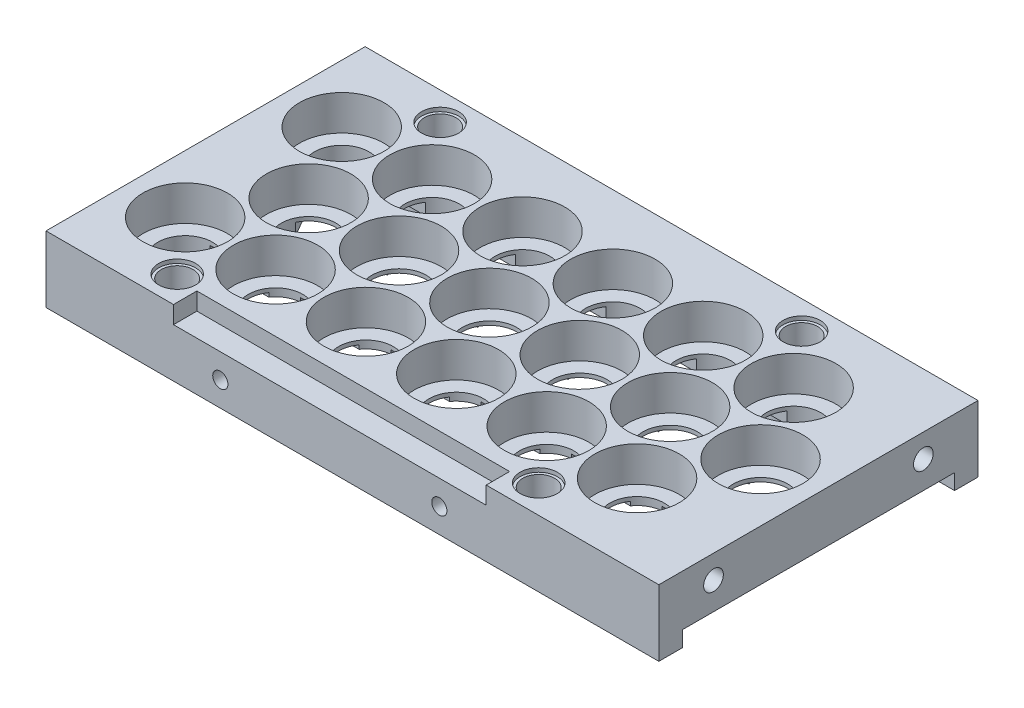
SolidWorks part; units mm, degrees
ref_plane "Front Plane" through (0, 0, 0) normal (0, 0, 1) x (1, 0, 0)
ref_plane "Top Plane" through (0, 0, 0) normal (0, 1, 0) x (1, 0, 0)
ref_plane "Right Plane" through (0, 0, 0) normal (1, 0, 0) x (0, 0, -1)
sketch "Sketch1" plane through (0, 0, 0) normal (0, 1, 0) x (1, 0, 0)
  line L0 (0, 0) -> (11.575, -20.0485) construction
  line L1 (11.575, -20.0485) -> (0, -40.097) construction
  line L2 (0, 0) -> (11.575, 0) construction
  line L3 (11.575, 0) -> (11.575, -20.0485) construction
  line L4 (11.575, -20.0485) -> (11.575, -40.097) construction
  line L5 (11.575, -40.097) -> (0, -40.097) construction
  line L6 (0, 0) -> (23.15, 0) construction
  line L7 (0, 0) -> (23.15, 0) construction
  line L8 (-14.825, -60.922) -> (142.15, -60.922)
  line L9 (-14.825, -60.922) -> (-14.825, 20.825)
  line L10 (-14.825, 20.825) -> (142.15, 20.825)
  line L11 (142.15, -60.922) -> (142.15, 20.825)
  circle A0 centre (0, 0) radius 10.825
  circle A1 centre (11.575, -20.0485) radius 10.825
  circle A2 centre (0, -40.097) radius 10.825
  circle A3 centre (23.15, 0) radius 10.825
  circle A4 centre (34.725, -20.0485) radius 10.825
  circle A5 centre (23.15, -40.097) radius 10.825
  circle A6 centre (46.3, 0) radius 10.825
  circle A7 centre (57.875, -20.0485) radius 10.825
  circle A8 centre (46.3, -40.097) radius 10.825
  circle A9 centre (69.45, 0) radius 10.825
  circle A10 centre (81.025, -20.0485) radius 10.825
  circle A11 centre (69.45, -40.097) radius 10.825
  circle A12 centre (92.6, 0) radius 10.825
  circle A13 centre (104.175, -20.0485) radius 10.825
  circle A14 centre (92.6, -40.097) radius 10.825
  circle A15 centre (115.75, 0) radius 10.825
  circle A16 centre (127.325, -20.0485) radius 10.825
  circle A17 centre (115.75, -40.097) radius 10.825
  circle A18 centre (0, 0) radius 7
  circle A19 centre (11.575, -20.0485) radius 7
  circle A20 centre (0, -40.097) radius 7
  circle A21 centre (23.15, 0) radius 7
  circle A22 centre (34.725, -20.0485) radius 7
  circle A23 centre (23.15, -40.097) radius 7
  circle A24 centre (46.3, 0) radius 7
  circle A25 centre (57.875, -20.0485) radius 7
  circle A26 centre (46.3, -40.097) radius 7
  circle A27 centre (69.45, 0) radius 7
  circle A28 centre (81.025, -20.0485) radius 7
  circle A29 centre (69.45, -40.097) radius 7
  circle A30 centre (92.6, 0) radius 7
  circle A31 centre (104.175, -20.0485) radius 7
  circle A32 centre (92.6, -40.097) radius 7
  circle A33 centre (115.75, 0) radius 7
  circle A34 centre (127.325, -20.0485) radius 7
  circle A35 centre (115.75, -40.097) radius 7
  dimension "D3" = 21.65
  dimension "D11" = 14
  dimension "D1" = 60
  dimension "D2" = 60
  dimension "D4" = 1.5
  dimension "D6" = 23.15
  dimension "D7" = 4
  dimension "D8" = 4
  dimension "D9" = 10
  dimension "D10" = 10
  dimension "D13" = 23.15
  dimension "D5" = 6
  dimension "D12" = 6
extrude "Boss-Extrude2" add sketch "Sketch1" along normal blind 11 contours L8 L11 L10 L9 A17 A16 A15 A14 A13 A12 A11 A10 A9 A8 A7 A6 A5 A4 A3 A2 A1 A0 region at (-13.0551, 0, 20.0485)
extrude "Boss-Extrude3" add sketch "Sketch1<3>" along normal blind 2 contours A0 A18 | A3 A21 | A6 A24 | A9 A27 | A12 A30 | A15 A33 | A1 A19 | A4 A22 | A7 A25 | A10 A28 | A13 A31 | A16 A34 | A17 A35 | A14 A32 | A11 A29 | A8 A26 | A5 A23 | A2 A20 region at (-10.5188, 0, 0) region at (1.0562, 0, 20.0485) region at (-10.5188, 0, 40.097) region at (12.6312, 0, 0) region at (24.2062, 0, 20.0485) region at (12.6312, 0, 40.097) region at (35.7812, 0, 0) region at (47.3562, 0, 20.0485) region at (35.7812, 0, 40.097) region at (58.9312, 0, 0) region at (70.5062, 0, 20.0485) region at (58.9312, 0, 40.097) region at (82.0812, 0, 0) region at (93.6562, 0, 20.0485) region at (82.0812, 0, 40.097) region at (105.2312, 0, 0) region at (116.8062, 0, 20.0485) region at (105.2312, 0, 40.097)
sketch "Sketch1<3>" plane through (0, 0, 0) normal (0, 1, 0) x (1, 0, 0) same geometry as "Sketch1"
sketch "Sketch2" plane through (0, 0, 0) normal (0, -1, 0) x (1, 0, 0)
  line L0 (0, 40.097) -> (11.575, 20.0485) construction
  line L1 (3.4641, 42.097) -> (15.0391, 22.0485)
  line L2 (-3.4641, 38.097) -> (8.1109, 18.0485)
  line L3 (11.575, 20.0485) -> (0, 0) construction
  line L4 (15.0391, 18.0485) -> (3.4641, -2)
  line L5 (8.1109, 22.0485) -> (-3.4641, 2)
  line L6 (19.6859, 38.097) -> (31.2609, 18.0485)
  line L7 (26.6141, 42.097) -> (38.1891, 22.0485)
  line L8 (31.2609, 22.0485) -> (19.6859, 2)
  line L9 (38.1891, 18.0485) -> (26.6141, -2)
  line L10 (23.15, 40.097) -> (34.725, 20.0485) construction
  line L11 (34.725, 20.0485) -> (23.15, 0) construction
  line L12 (42.8359, 38.097) -> (54.4109, 18.0485)
  line L13 (49.7641, 42.097) -> (61.3391, 22.0485)
  line L14 (54.4109, 22.0485) -> (42.8359, 2)
  line L15 (61.3391, 18.0485) -> (49.7641, -2)
  line L16 (46.3, 40.097) -> (57.875, 20.0485) construction
  line L17 (57.875, 20.0485) -> (46.3, 0) construction
  line L18 (65.9859, 38.097) -> (77.5609, 18.0485)
  line L19 (72.9141, 42.097) -> (84.4891, 22.0485)
  line L20 (77.5609, 22.0485) -> (65.9859, 2)
  line L21 (84.4891, 18.0485) -> (72.9141, -2)
  line L22 (69.45, 40.097) -> (81.025, 20.0485) construction
  line L23 (81.025, 20.0485) -> (69.45, 0) construction
  line L24 (89.1359, 38.097) -> (100.7109, 18.0485)
  line L25 (96.0641, 42.097) -> (107.6391, 22.0485)
  line L26 (100.7109, 22.0485) -> (89.1359, 2)
  line L27 (107.6391, 18.0485) -> (96.0641, -2)
  line L28 (92.6, 40.097) -> (104.175, 20.0485) construction
  line L29 (104.175, 20.0485) -> (92.6, 0) construction
  line L30 (112.2859, 38.097) -> (123.8609, 18.0485)
  line L31 (119.2141, 42.097) -> (130.7891, 22.0485)
  line L32 (123.8609, 22.0485) -> (112.2859, 2)
  line L33 (130.7891, 18.0485) -> (119.2141, -2)
  line L34 (115.75, 40.097) -> (127.325, 20.0485) construction
  line L35 (127.325, 20.0485) -> (115.75, 0) construction
  line L36 (-3.4641, 38.097) -> (19.6859, 38.097) construction
  line L37 (0, 40.097) -> (115.75, 40.097) construction
  line L38 (0, 44.097) -> (115.75, 44.097)
  line L39 (0, 36.097) -> (115.75, 36.097)
  line L40 (11.575, 20.0485) -> (127.325, 20.0485) construction
  line L41 (11.575, 24.0485) -> (127.325, 24.0485)
  line L42 (11.575, 16.0485) -> (127.325, 16.0485)
  line L43 (0, 0) -> (115.75, 0) construction
  line L44 (0, 4) -> (115.75, 4)
  line L45 (0, -4) -> (115.75, -4)
  arc A0 (3.4641, 42.097) -> (-3.4641, 38.097) centre (0, 40.097) ccw
  arc A1 (8.1109, 18.0485) -> (15.0391, 22.0485) centre (11.575, 20.0485) ccw
  arc A2 (15.0391, 18.0485) -> (8.1109, 22.0485) centre (11.575, 20.0485) ccw
  arc A3 (-3.4641, 2) -> (3.4641, -2) centre (0, 0) ccw
  arc A4 (26.6141, 42.097) -> (19.6859, 38.097) centre (23.15, 40.097) ccw
  arc A5 (31.2609, 18.0485) -> (38.1891, 22.0485) centre (34.725, 20.0485) ccw
  arc A6 (38.1891, 18.0485) -> (31.2609, 22.0485) centre (34.725, 20.0485) ccw
  arc A7 (19.6859, 2) -> (26.6141, -2) centre (23.15, 0) ccw
  arc A8 (49.7641, 42.097) -> (42.8359, 38.097) centre (46.3, 40.097) ccw
  arc A9 (54.4109, 18.0485) -> (61.3391, 22.0485) centre (57.875, 20.0485) ccw
  arc A10 (61.3391, 18.0485) -> (54.4109, 22.0485) centre (57.875, 20.0485) ccw
  arc A11 (42.8359, 2) -> (49.7641, -2) centre (46.3, 0) ccw
  arc A12 (72.9141, 42.097) -> (65.9859, 38.097) centre (69.45, 40.097) ccw
  arc A13 (77.5609, 18.0485) -> (84.4891, 22.0485) centre (81.025, 20.0485) ccw
  arc A14 (84.4891, 18.0485) -> (77.5609, 22.0485) centre (81.025, 20.0485) ccw
  arc A15 (65.9859, 2) -> (72.9141, -2) centre (69.45, 0) ccw
  arc A16 (96.0641, 42.097) -> (89.1359, 38.097) centre (92.6, 40.097) ccw
  arc A17 (100.7109, 18.0485) -> (107.6391, 22.0485) centre (104.175, 20.0485) ccw
  arc A18 (107.6391, 18.0485) -> (100.7109, 22.0485) centre (104.175, 20.0485) ccw
  arc A19 (89.1359, 2) -> (96.0641, -2) centre (92.6, 0) ccw
  arc A20 (119.2141, 42.097) -> (112.2859, 38.097) centre (115.75, 40.097) ccw
  arc A21 (123.8609, 18.0485) -> (130.7891, 22.0485) centre (127.325, 20.0485) ccw
  arc A22 (130.7891, 18.0485) -> (123.8609, 22.0485) centre (127.325, 20.0485) ccw
  arc A23 (112.2859, 2) -> (119.2141, -2) centre (115.75, 0) ccw
  arc A24 (0, 44.097) -> (0, 36.097) centre (0, 40.097) ccw
  arc A25 (115.75, 36.097) -> (115.75, 44.097) centre (115.75, 40.097) ccw
  arc A26 (11.575, 24.0485) -> (11.575, 16.0485) centre (11.575, 20.0485) ccw
  arc A27 (127.325, 16.0485) -> (127.325, 24.0485) centre (127.325, 20.0485) ccw
  arc A28 (0, 4) -> (0, -4) centre (0, 0) ccw
  arc A29 (115.75, -4) -> (115.75, 4) centre (115.75, 0) ccw
  point P3 (5.7875, 30.0727)
  point P8 (5.7875, 10.0242)
  point P18 (28.9375, 30.0727)
  point P25 (28.9375, 10.0242)
  point P34 (52.0875, 30.0727)
  point P39 (52.0875, 10.0242)
  point P48 (75.2375, 30.0727)
  point P53 (75.2375, 10.0242)
  point P62 (98.3875, 30.0727)
  point P67 (98.3875, 10.0242)
  point P76 (121.5375, 30.0727)
  point P81 (121.5375, 10.0242)
  point P91 (57.875, 40.097)
  point P96 (69.45, 20.0485)
  point P103 (57.875, 0)
  circle M62 centre (0, 0) radius 7
  circle M63 centre (23.15, 0) radius 7
  circle M64 centre (46.3, 0) radius 7
  circle M65 centre (69.45, 0) radius 7
  circle M66 centre (92.6, 0) radius 7
  circle M67 centre (115.75, 0) radius 7
  circle M68 centre (11.575, 20.0485) radius 7
  circle M69 centre (34.725, 20.0485) radius 7
  circle M70 centre (57.875, 20.0485) radius 7
  circle M71 centre (81.025, 20.0485) radius 7
  circle M72 centre (104.175, 20.0485) radius 7
  circle M73 centre (127.325, 20.0485) radius 7
  circle M74 centre (115.75, 40.097) radius 7
  circle M75 centre (92.6, 40.097) radius 7
  circle M76 centre (69.45, 40.097) radius 7
  circle M77 centre (46.3, 40.097) radius 7
  circle M78 centre (23.15, 40.097) radius 7
  circle M79 centre (0, 40.097) radius 7
  dimension "D1" = 8
  dimension "D3" = 23.15
  dimension "D4" = 8
  dimension "D5" = 8
  dimension "D6" = 8
extrude "Cut-Extrude1" cut sketch "Sketch2" against normal blind 1 contours L1 L39 L38 M78 M79 | L7 L39 L38 M77 M78 | L39 L2 L1 M79 M68 | L42 L8 L6 L41 M68 M69 | L6 L41 L7 L39 M69 M78 | L12 L41 L13 L39 M70 M77 | L13 L39 L38 M76 M77 | L18 L41 L19 L39 M71 M76 | L19 L39 L38 M75 M76 | L24 L41 L25 L39 M72 M75 | L25 L39 L38 M74 M75 | L30 L41 L31 M73 M74 | L42 L32 L30 L41 M72 M73 | L42 L26 L24 L41 M71 M72 | L42 L20 L18 L41 M70 M71 | L42 L14 L12 L41 M69 M70 | L45 L44 L4 M62 M63 | L44 L4 L5 M62 M68 | L45 L44 L9 M63 M64 | L45 L44 L15 M64 M65 | L45 L44 L21 M65 M66 | L45 L44 L27 M66 M67 | L44 L27 L42 L26 M66 M72 | L42 L32 L33 M67 M73 | L44 L21 L42 L20 M65 M71 | L44 L15 L42 L14 M64 M70 | L39 L13 M77 | L39 L25 M75 | L39 L19 M76 | L41 L6 M69 | L44 L4 M62 | L44 L15 M64 | L44 L21 M65 | L44 L27 M66 | L41 L30 M73 | L32 L42 M73 | L41 L24 M72 | L26 L42 M72 | L41 L18 M71 | L20 L42 M71 | L41 L12 M70 | L14 L42 M70 | L44 L9 L42 L8 M63 M69 | L8 L42 M69 | L39 L7 M78 | L39 L1 M79 | L44 A29 L45 A28 region at (11.6138, 0, 40.1242) region at (6.3461, 0, 36.4331) region at (5.7834, 0, 30.0255) region at (23.0718, 0, 20.0485) region at (28.9375, 0, 30.0727) region at (34.7638, 0, 40.1242) region at (28.3789, 0, 23.7124) region at (5.7834, 0, 10.0715) region at (29.4961, 0, 36.4331) region at (57.9138, 0, 40.1242) region at (28.3789, 0, 16.3846) region at (28.9375, 0, 10.0242) region at (6.3461, 0, 3.6639) region at (11.6138, 0, -0.0272) region at (52.0875, 0, 30.0727) region at (46.2218, 0, 20.0485) region at (52.6461, 0, 36.4331) region at (81.0638, 0, 40.1242) region at (51.5289, 0, 23.7124) region at (34.7638, 0, -0.0272) region at (75.2375, 0, 30.0727) region at (75.7961, 0, 36.4331) region at (104.2138, 0, 40.1242) region at (74.6789, 0, 23.7124) region at (69.3718, 0, 20.0485) region at (51.5289, 0, 16.3846) region at (52.0875, 0, 10.0242) region at (57.9138, 0, -0.0272) region at (98.3875, 0, 30.0727) region at (98.9461, 0, 36.4331) region at (97.8289, 0, 23.7124) region at (92.5218, 0, 20.0485) region at (74.6789, 0, 16.3846) region at (52.6461, 0, 3.6639) region at (81.0638, 0, -0.0272) region at (121.5416, 0, 30.12) region at (75.2375, 0, 10.0242) region at (120.9789, 0, 23.7124) region at (115.6718, 0, 20.0485) region at (97.8289, 0, 16.3846) region at (75.7961, 0, 3.6639) region at (104.2138, 0, -0.0272) region at (98.3875, 0, 10.0242) region at (121.5416, 0, 9.977) region at (120.9789, 0, 16.3846) region at (98.9461, 0, 3.6639)
sketch "Sketch9" plane through (0, 11, 0) normal (0, 1, 0) x (1, 0, 0)
  line L0 (11.575, -60.922) -> (11.575, 20.825)
  line L1 (-14.825, 20.825) -> (142.15, 20.825) construction
  line L2 (104.175, 20.825) -> (104.175, -60.922)
  line L3 (-14.825, -60.922) -> (142.15, -60.922) construction
  circle A0 centre (11.575, 13.625) radius 4.0767
  circle A1 centre (11.575, -53.722) radius 4.0767
  circle A2 centre (104.175, -53.722) radius 4.0767
  circle A3 centre (104.175, 13.625) radius 4.0767
  point P0 (11.575, 13.625)
  point P7 (11.575, -20.0485)
  point P15 (104.175, -20.0485)
  point P20 (104.175, 13.625)
  point P21 (104.175, -53.722)
  point P22 (11.575, -53.722)
  dimension "D5" = 8.1534
  dimension "D1" = 7.2
  dimension "D4" = 7.2
extrude "Cut-Extrude3" cut sketch "Sketch9" against normal up to next contours A2 | A1 | A0 | A3
sketch "Sketch10" plane through (0, 11, 0) normal (0, 1, 0) x (1, 0, 0)
  circle A0 centre (11.575, 13.625) radius 4.7625
  circle A1 centre (104.175, 13.625) radius 4.7625
  circle A2 centre (104.175, -53.722) radius 4.7625
  circle A3 centre (11.575, -53.722) radius 4.7625
  dimension "D1" = 9.525
extrude "Cut-Extrude4" cut sketch "Sketch10" against normal blind 1
sketch "Sketch13" plane through (0, 0, 0) normal (0, -1, 0) x (1, 0, 0)
  line L0 (142.15, 60.922) -> (142.15, -20.825) construction
  line L5 (3.575, 53.722) -> (3.575, 60.922)
  line L8 (-14.825, 60.922) -> (142.15, 60.922) construction
  line L9 (3.575, 60.922) -> (19.575, 60.922)
  line L10 (19.575, 60.922) -> (19.575, 53.722)
  line L12 (57.875, 20.0485) -> (57.875, -20.825) construction
  line L13 (-14.825, -20.825) -> (142.15, -20.825) construction
  line L14 (11.575, 20.0485) -> (127.325, 20.0485) construction
  line L16 (96.175, 60.922) -> (96.175, 53.722)
  line L17 (112.175, 60.922) -> (96.175, 60.922)
  line L18 (112.175, 53.722) -> (112.175, 60.922)
  line L19 (-14.825, 60.922) -> (142.15, 60.922)
  line L20 (-14.825, 60.922) -> (-14.825, 54.922)
  line L21 (-14.825, 54.922) -> (142.15, 54.922)
  line L22 (142.15, 60.922) -> (142.15, 54.922)
  line L23 (142.15, -20.825) -> (142.15, -14.825)
  line L24 (-14.825, -14.825) -> (142.15, -14.825)
  line L25 (-14.825, -20.825) -> (-14.825, -14.825)
  line L26 (-14.825, -20.825) -> (142.15, -20.825)
  line L27 (112.175, -13.625) -> (112.175, -20.825)
  line L28 (112.175, -20.825) -> (96.175, -20.825)
  line L29 (96.175, -20.825) -> (96.175, -13.625)
  line L32 (19.575, -20.825) -> (19.575, -13.625)
  line L33 (3.575, -20.825) -> (19.575, -20.825)
  line L34 (3.575, -13.625) -> (3.575, -20.825)
  circle A4 centre (11.575, 53.722) radius 6.5
  circle A5 centre (11.575, 53.722) radius 8
  circle A6 centre (104.175, 53.722) radius 8
  circle A7 centre (104.175, 53.722) radius 6.5
  circle A8 centre (104.175, -13.625) radius 6.5
  circle A9 centre (104.175, -13.625) radius 8
  circle A10 centre (11.575, -13.625) radius 8
  circle A11 centre (11.575, -13.625) radius 6.5
  line M15 (142.15, 60.922) -> (-14.825, 60.922)
  line M16 (-14.825, 60.922) -> (-14.825, -20.825)
  line M17 (-14.825, -20.825) -> (142.15, -20.825)
  line M18 (142.15, -20.825) -> (142.15, 60.922)
  dimension "D1" = 13
  dimension "D2" = 16
  dimension "D3" = 6
extrude "Boss-Extrude7" add sketch "Sketch13" along normal blind 6 contours L21 L5 M16 M15 | A5 L5 L21 M15 | A5 L21 L10 M15 | L10 L21 L16 M15 | L21 A5 L19 A4 | A5 L21 A4 | L21 A6 L16 M15 | L21 A7 A6 L19 | L21 A7 A6 | A6 L21 L18 M15 | L18 L21 M18 M15 | A9 L24 L29 L26 | L28 A9 L24 A8 | A9 L26 L27 L24 | L24 L27 L26 M18 | L32 L26 L29 L24 | L24 A9 A8 | L34 L24 M16 M17 | L26 A10 L24 L34 | L24 A11 A10 | L24 A11 A10 L33 | L24 A10 L26 L32 region at (3.7817, 0, 54.3098) region at (-5.625, 0, 57.922) region at (4.8282, 0, 59.2567) region at (5.2714, 0, 58.3681) region at (18.3218, 0, 59.2567) region at (57.875, 0, 57.922) region at (-5.625, 0, -17.825) region at (97.4282, 0, 59.2567) region at (4.8282, 0, -19.1597) region at (96.3817, 0, 54.3098) region at (97.8714, 0, 58.3681) region at (3.7817, 0, -14.2128) region at (4.4261, 0, -14.9942) region at (110.9218, 0, 59.2567) region at (127.1625, 0, 57.922) region at (18.3218, 0, -19.1597) region at (57.875, 0, -17.825) region at (97.4282, 0, -19.1597) region at (127.1625, 0, -17.825) region at (96.3817, 0, -14.2128) region at (97.0261, 0, -14.9942) region at (110.9218, 0, -19.1597)
sketch "Sketch14" plane through (0, 0, 0) normal (0, -1, 0) x (1, 0, 0)
  line L2 (142.15, 54.922) -> (142.15, -14.825) construction
  line L4 (5.2386, 17.0736) -> (-0.5918, 6.9749) construction
  line L5 (5.7446, -4) -> (17.4054, -4) construction
  line L6 (28.8946, -4) -> (40.5554, -4) construction
  line L7 (52.0446, -4) -> (63.7054, -4) construction
  line L8 (75.1946, -4) -> (86.8554, -4) construction
  line L9 (98.3446, -4) -> (110.0054, -4) construction
  line L10 (127.9168, 13.0736) -> (122.0864, 2.9749) construction
  line L11 (122.0864, 37.122) -> (127.9168, 27.0234) construction
  line L12 (98.3446, 44.097) -> (110.0054, 44.097) construction
  line L13 (75.1946, 44.097) -> (86.8554, 44.097) construction
  line L14 (52.0446, 44.097) -> (63.7054, 44.097) construction
  line L15 (28.8946, 44.097) -> (40.5554, 44.097) construction
  line L16 (-0.5918, 33.122) -> (5.2386, 23.0234) construction
  line L17 (5.7446, 44.097) -> (17.4054, 44.097) construction
  line L20 (142.15, 54.922) -> (142.15, -14.825)
  line L22 (5.2386, 17.0736) -> (-0.5918, 6.9749)
  line L23 (5.7446, -4) -> (17.4054, -4)
  line L24 (28.8946, -4) -> (40.5554, -4)
  line L25 (52.0446, -4) -> (63.7054, -4)
  line L26 (75.1946, -4) -> (86.8554, -4)
  line L27 (98.3446, -4) -> (110.0054, -4)
  line L28 (127.9168, 13.0736) -> (122.0864, 2.9749)
  line L29 (122.0864, 37.122) -> (127.9168, 27.0234)
  line L30 (98.3446, 44.097) -> (110.0054, 44.097)
  line L31 (75.1946, 44.097) -> (86.8554, 44.097)
  line L32 (52.0446, 44.097) -> (63.7054, 44.097)
  line L33 (28.8946, 44.097) -> (40.5554, 44.097)
  line L34 (-0.5918, 33.122) -> (5.2386, 23.0234)
  line L35 (5.7446, 44.097) -> (17.4054, 44.097)
  line L36 (112.0845, -14.825) -> (142.15, -14.825) construction
  line L37 (19.4845, -14.825) -> (96.2655, -14.825) construction
  line L38 (-14.825, -14.825) -> (3.6655, -14.825) construction
  line L39 (-14.825, 54.922) -> (-14.825, -14.825) construction
  line L40 (112.0845, 54.922) -> (142.15, 54.922) construction
  line L41 (19.4845, 54.922) -> (96.2655, 54.922) construction
  line L42 (-14.825, 54.922) -> (3.6655, 54.922) construction
  line L43 (112.0845, -14.825) -> (142.15, -14.825)
  line L44 (19.4845, -14.825) -> (96.2655, -14.825)
  line L45 (-14.825, -14.825) -> (3.6655, -14.825)
  line L46 (-14.825, 54.922) -> (-14.825, -14.825)
  line L47 (112.0845, 54.922) -> (142.15, 54.922)
  line L48 (19.4845, 54.922) -> (96.2655, 54.922)
  line L49 (-14.825, 54.922) -> (3.6655, 54.922)
  arc A3 (5.2386, 23.0234) -> (5.2386, 17.0736) centre (11.575, 20.0485) ccw construction
  arc A4 (-0.5918, 6.9749) -> (5.7446, -4) centre (0, 0) ccw construction
  arc A5 (17.4054, -4) -> (28.8946, -4) centre (23.15, 0) ccw construction
  arc A6 (40.5554, -4) -> (52.0446, -4) centre (46.3, 0) ccw construction
  arc A7 (63.7054, -4) -> (75.1946, -4) centre (69.45, 0) ccw construction
  arc A8 (86.8554, -4) -> (98.3446, -4) centre (92.6, 0) ccw construction
  arc A9 (110.0054, -4) -> (122.0864, 2.9749) centre (115.75, 0) ccw construction
  arc A10 (127.9168, 13.0736) -> (127.9168, 27.0234) centre (127.325, 20.0485) ccw construction
  arc A11 (122.0864, 37.122) -> (110.0054, 44.097) centre (115.75, 40.097) ccw construction
  arc A12 (98.3446, 44.097) -> (86.8554, 44.097) centre (92.6, 40.097) ccw construction
  arc A13 (75.1946, 44.097) -> (63.7054, 44.097) centre (69.45, 40.097) ccw construction
  arc A14 (52.0446, 44.097) -> (40.5554, 44.097) centre (46.3, 40.097) ccw construction
  arc A16 (28.8946, 44.097) -> (17.4054, 44.097) centre (23.15, 40.097) ccw construction
  arc A17 (5.7446, 44.097) -> (-0.5918, 33.122) centre (0, 40.097) ccw construction
  arc A21 (5.2386, 23.0234) -> (5.2386, 17.0736) centre (11.575, 20.0485) ccw
  arc A22 (-0.5918, 6.9749) -> (5.7446, -4) centre (0, 0) ccw
  arc A23 (17.4054, -4) -> (28.8946, -4) centre (23.15, 0) ccw
  arc A24 (40.5554, -4) -> (52.0446, -4) centre (46.3, 0) ccw
  arc A25 (63.7054, -4) -> (75.1946, -4) centre (69.45, 0) ccw
  arc A26 (86.8554, -4) -> (98.3446, -4) centre (92.6, 0) ccw
  arc A27 (110.0054, -4) -> (122.0864, 2.9749) centre (115.75, 0) ccw
  arc A28 (127.9168, 13.0736) -> (127.9168, 27.0234) centre (127.325, 20.0485) ccw
  arc A29 (122.0864, 37.122) -> (110.0054, 44.097) centre (115.75, 40.097) ccw
  arc A30 (98.3446, 44.097) -> (86.8554, 44.097) centre (92.6, 40.097) ccw
  arc A31 (75.1946, 44.097) -> (63.7054, 44.097) centre (69.45, 40.097) ccw
  arc A32 (52.0446, 44.097) -> (40.5554, 44.097) centre (46.3, 40.097) ccw
  arc A34 (28.8946, 44.097) -> (17.4054, 44.097) centre (23.15, 40.097) ccw
  arc A35 (5.7446, 44.097) -> (-0.5918, 33.122) centre (0, 40.097) ccw
  arc A36 (112.0845, -14.825) -> (96.2655, -14.825) centre (104.175, -13.625) ccw construction
  arc A37 (19.4845, -14.825) -> (3.6655, -14.825) centre (11.575, -13.625) ccw construction
  arc A38 (96.2655, 54.922) -> (112.0845, 54.922) centre (104.175, 53.722) ccw construction
  arc A39 (3.6655, 54.922) -> (19.4845, 54.922) centre (11.575, 53.722) ccw construction
  arc A40 (112.0845, -14.825) -> (96.2655, -14.825) centre (104.175, -13.625) ccw
  arc A41 (19.4845, -14.825) -> (3.6655, -14.825) centre (11.575, -13.625) ccw
  arc A42 (96.2655, 54.922) -> (112.0845, 54.922) centre (104.175, 53.722) ccw
  arc A43 (3.6655, 54.922) -> (19.4845, 54.922) centre (11.575, 53.722) ccw
extrude "Boss-Extrude9" add sketch "Sketch14" along normal blind 2
sketch "Sketch16" plane through (0, 0, 0) normal (0, -1, 0) x (1, 0, 0)
  line L0 (17.4054, 36.097) -> (12.1668, 27.0234) construction
  line L1 (12.1668, 27.0234) -> (17.3196, 24.0485) construction
  line L2 (17.3196, 24.0485) -> (22.5582, 33.122) construction
  line L3 (22.5582, 33.122) -> (17.4054, 36.097) construction
  line L4 (14.7861, 31.5602) -> (19.9389, 28.5853) construction
  line L5 (15.5361, 32.8592) -> (20.6889, 29.8843)
  line L6 (14.0361, 30.2612) -> (19.1889, 27.2862)
  line L7 (11.575, 20.0485) -> (126.446, 20.0485) construction
  line L8 (40.5554, 36.097) -> (35.3168, 27.0234) construction
  line L9 (35.3168, 27.0234) -> (40.4696, 24.0485) construction
  line L10 (40.4696, 24.0485) -> (45.7082, 33.122) construction
  line L11 (45.7082, 33.122) -> (40.5554, 36.097) construction
  line L12 (37.9361, 31.5602) -> (43.0889, 28.5853) construction
  line L13 (38.6861, 32.8592) -> (43.8389, 29.8843)
  line L14 (37.1861, 30.2612) -> (42.3389, 27.2862)
  line L15 (63.7054, 36.097) -> (58.4668, 27.0234) construction
  line L16 (58.4668, 27.0234) -> (63.6196, 24.0485) construction
  line L17 (63.6196, 24.0485) -> (68.8582, 33.122) construction
  line L18 (68.8582, 33.122) -> (63.7054, 36.097) construction
  line L19 (61.0861, 31.5602) -> (66.2389, 28.5853) construction
  line L20 (61.8361, 32.8592) -> (66.9889, 29.8843)
  line L21 (60.3361, 30.2612) -> (65.4889, 27.2862)
  line L22 (86.8554, 36.097) -> (81.6168, 27.0234) construction
  line L23 (81.6168, 27.0234) -> (86.7696, 24.0485) construction
  line L24 (86.7696, 24.0485) -> (92.0082, 33.122) construction
  line L25 (92.0082, 33.122) -> (86.8554, 36.097) construction
  line L26 (84.2361, 31.5602) -> (89.3889, 28.5853) construction
  line L27 (84.9861, 32.8592) -> (90.1389, 29.8843)
  line L28 (83.4861, 30.2612) -> (88.6389, 27.2862)
  line L29 (110.0054, 36.097) -> (104.7668, 27.0234) construction
  line L30 (104.7668, 27.0234) -> (109.9196, 24.0485) construction
  line L31 (109.9196, 24.0485) -> (115.1582, 33.122) construction
  line L32 (115.1582, 33.122) -> (110.0054, 36.097) construction
  line L33 (107.3861, 31.5602) -> (112.5389, 28.5853) construction
  line L34 (108.1361, 32.8592) -> (113.2889, 29.8843)
  line L35 (106.6361, 30.2612) -> (111.7889, 27.2862)
  line L36 (14.7861, 8.5368) -> (19.9389, 11.5117) construction
  line L37 (15.5361, 7.2377) -> (20.6889, 10.2127)
  line L38 (14.0361, 9.8358) -> (19.1889, 12.8108)
  line L39 (37.9361, 8.5368) -> (43.0889, 11.5117) construction
  line L40 (38.6861, 7.2377) -> (43.8389, 10.2127)
  line L41 (37.1861, 9.8358) -> (42.3389, 12.8108)
  line L42 (61.0861, 8.5368) -> (66.2389, 11.5117) construction
  line L43 (61.8361, 7.2377) -> (66.9889, 10.2127)
  line L44 (60.3361, 9.8358) -> (65.4889, 12.8108)
  line L45 (84.2361, 8.5368) -> (89.3889, 11.5117) construction
  line L46 (84.9861, 7.2377) -> (90.1389, 10.2127)
  line L47 (83.4861, 9.8358) -> (88.6389, 12.8108)
  line L48 (107.3861, 8.5368) -> (112.5389, 11.5117) construction
  line L49 (108.1361, 7.2377) -> (113.2889, 10.2127)
  line L50 (106.6361, 9.8358) -> (111.7889, 12.8108)
  line L51 (115.1582, 6.9749) -> (110.0054, 4) construction
  line L52 (109.9196, 16.0485) -> (115.1582, 6.9749) construction
  line L53 (104.7668, 13.0736) -> (109.9196, 16.0485) construction
  line L54 (110.0054, 4) -> (104.7668, 13.0736) construction
  line L55 (92.0082, 6.9749) -> (86.8554, 4) construction
  line L56 (86.7696, 16.0485) -> (92.0082, 6.9749) construction
  line L57 (81.6168, 13.0736) -> (86.7696, 16.0485) construction
  line L58 (86.8554, 4) -> (81.6168, 13.0736) construction
  line L59 (68.8582, 6.9749) -> (63.7054, 4) construction
  line L60 (63.6196, 16.0485) -> (68.8582, 6.9749) construction
  line L61 (58.4668, 13.0736) -> (63.6196, 16.0485) construction
  line L62 (63.7054, 4) -> (58.4668, 13.0736) construction
  line L63 (45.7082, 6.9749) -> (40.5554, 4) construction
  line L64 (40.4696, 16.0485) -> (45.7082, 6.9749) construction
  line L65 (35.3168, 13.0736) -> (40.4696, 16.0485) construction
  line L66 (40.5554, 4) -> (35.3168, 13.0736) construction
  line L67 (22.5582, 6.9749) -> (17.4054, 4) construction
  line L68 (17.3196, 16.0485) -> (22.5582, 6.9749) construction
  line L69 (12.1668, 13.0736) -> (17.3196, 16.0485) construction
  line L70 (17.4054, 4) -> (12.1668, 13.0736) construction
  arc A0 (15.5361, 32.8592) -> (14.0361, 30.2612) centre (14.7861, 31.5602) ccw
  arc A1 (19.1889, 27.2862) -> (20.6889, 29.8843) centre (19.9389, 28.5853) ccw
  arc A2 (38.6861, 32.8592) -> (37.1861, 30.2612) centre (37.9361, 31.5602) ccw
  arc A3 (42.3389, 27.2862) -> (43.8389, 29.8843) centre (43.0889, 28.5853) ccw
  arc A4 (61.8361, 32.8592) -> (60.3361, 30.2612) centre (61.0861, 31.5602) ccw
  arc A5 (65.4889, 27.2862) -> (66.9889, 29.8843) centre (66.2389, 28.5853) ccw
  arc A6 (84.9861, 32.8592) -> (83.4861, 30.2612) centre (84.2361, 31.5602) ccw
  arc A7 (88.6389, 27.2862) -> (90.1389, 29.8843) centre (89.3889, 28.5853) ccw
  arc A8 (108.1361, 32.8592) -> (106.6361, 30.2612) centre (107.3861, 31.5602) ccw
  arc A9 (111.7889, 27.2862) -> (113.2889, 29.8843) centre (112.5389, 28.5853) ccw
  arc A10 (40.5554, 36.097) -> (45.7082, 33.122) centre (46.3, 40.097) ccw construction
  arc A11 (15.5361, 7.2377) -> (14.0361, 9.8358) centre (14.7861, 8.5368) cw
  arc A12 (19.1889, 12.8108) -> (20.6889, 10.2127) centre (19.9389, 11.5117) cw
  arc A13 (38.6861, 7.2377) -> (37.1861, 9.8358) centre (37.9361, 8.5368) cw
  arc A14 (42.3389, 12.8108) -> (43.8389, 10.2127) centre (43.0889, 11.5117) cw
  arc A15 (61.8361, 7.2377) -> (60.3361, 9.8358) centre (61.0861, 8.5368) cw
  arc A16 (65.4889, 12.8108) -> (66.9889, 10.2127) centre (66.2389, 11.5117) cw
  arc A17 (84.9861, 7.2377) -> (83.4861, 9.8358) centre (84.2361, 8.5368) cw
  arc A18 (88.6389, 12.8108) -> (90.1389, 10.2127) centre (89.3889, 11.5117) cw
  arc A19 (108.1361, 7.2377) -> (106.6361, 9.8358) centre (107.3861, 8.5368) cw
  arc A20 (111.7889, 12.8108) -> (113.2889, 10.2127) centre (112.5389, 11.5117) cw
  point P10 (17.3625, 30.0727)
  point P25 (40.5125, 30.0727)
  point P36 (63.6625, 30.0727)
  point P47 (86.8125, 30.0727)
  point P58 (109.9625, 30.0727)
  point P68 (17.3625, 10.0242)
  point P75 (40.5125, 10.0242)
  point P82 (63.6625, 10.0242)
  point P89 (86.8125, 10.0242)
  point P96 (109.9625, 10.0242)
  dimension "D1" = 1.5
  dimension "D2" = 5
extrude "Boss-Extrude10" add sketch "Sketch16" along normal blind 2
sketch "Sketch17" plane through (0, -2, 0) normal (0, -1, 0) x (-1, 0, 0)
  line L0 (-57.875, -44.097) -> (-57.875, -54.922) construction
  line L1 (-63.7054, -44.097) -> (-52.0446, -44.097) construction
  line L2 (-19.4845, -54.922) -> (-96.2655, -54.922) construction
  line L3 (-142.15, 14.825) -> (-142.15, -54.922) construction
  line L4 (14.825, -54.922) -> (14.825, 14.825) construction
  line L5 (8.825, -49.5095) -> (-57.875, -49.5095) construction
  line L6 (-57.875, -49.5095) -> (-132.15, -49.5095) construction
  line L7 (-127.325, -20.0485) -> (-11.575, -20.0485)
  line L8 (-57.875, 9.4125) -> (-132.15, 9.4125) construction
  line L9 (8.825, 9.4125) -> (-57.875, 9.4125) construction
  line L10 (-57.875, 4) -> (-57.875, 14.825) construction
  circle A0 centre (8.825, -49.5095) radius 1.9431
  circle A1 centre (-57.875, -49.5095) radius 1.9431
  circle A2 centre (-132.15, -49.5095) radius 1.9431
  circle A3 centre (-132.15, 9.4125) radius 1.9431
  circle A4 centre (-57.875, 9.4125) radius 1.9431
  circle A5 centre (8.825, 9.4125) radius 1.9431
  dimension "D3" = 6
  dimension "D1" = 3.8862
  dimension "D2" = 10
extrude "Cut-Extrude5" cut sketch "Sketch17" against normal blind 4 contours A3 | A2 | A4 | A5 | A0 | A1 region at (-8.825, -2, 49.5095) region at (57.875, -2, 49.5095) region at (132.15, -2, 49.5095) region at (132.15, -2, -9.4125) region at (57.875, -2, -9.4125) region at (-8.825, -2, -9.4125)
sketch "Sketch19" plane through (0, 0, 60.922) normal (0, 0, 1) x (1, 0, 0)
  line L0 (11.575, 11) -> (104.175, 11)
  line L1 (-14.825, 11) -> (142.15, 11) construction
  line L2 (97.925, 11) -> (17.825, 11)
  line L3 (17.825, 11) -> (97.925, 11)
  line L4 (17.825, 11) -> (17.825, 6.525)
  line L5 (97.925, 11) -> (97.925, 6.525)
  line L6 (17.825, 6.525) -> (97.925, 6.525)
  point P5 (57.875, 11)
  point P9 (57.875, 11)
  dimension "D1" = 92.6
  dimension "D2" = 26.4
  dimension "D3" = 80.1
  dimension "D4" = 4.475
extrude "Cut-Extrude6" cut sketch "Sketch19" against normal blind 6 contours L4 L6 L5 L0 region at (57.875, 8.7625, 60.922)
sketch "Sketch20" plane through (0, 0, 60.922) normal (0, 0, 1) x (1, 0, 0)
  line L0 (29.825, 6.525) -> (85.925, 6.525)
  line L1 (29.825, 6.525) -> (29.825, 0.2625)
  line L2 (85.925, 6.525) -> (85.925, 0.2625)
  line L3 (29.825, 0.2625) -> (85.925, 0.2625)
  line L4 (29.825, 6.525) -> (17.825, 6.525) construction
  line L5 (85.925, 6.525) -> (97.925, 6.525) construction
  line L6 (57.875, 6.525) -> (57.875, -6)
  line L9 (142.15, -6) -> (-14.825, -6) construction
  circle A0 centre (29.825, 0.2625) radius 1.9431
  circle A1 centre (85.925, 0.2625) radius 1.9431
  point P9 (57.875, 0.2625)
  dimension "D2" = 3.8862
  dimension "D1" = 12
extrude "Cut-Extrude7" cut sketch "Sketch20" against normal blind 3.8862 contours L1 A0 L3 | L3 A0 L1 | L3 A1 L2 | L2 A1 L3 region at (30.6497, 1.0872, 60.922) region at (29.5501, -0.0124, 60.922) region at (86.1999, -0.0124, 60.922) region at (85.1003, 1.0872, 60.922)
sketch "Sketch22" plane through (142.15, 0, 0) normal (1, 0, 0) x (0, 0, -1)
  line L0 (-46.922, 5) -> (-60.922, 5)
  line L1 (-60.922, 11) -> (-60.922, -6) construction
  line L2 (6.825, 5) -> (20.825, 5)
  line L3 (20.825, 11) -> (20.825, -6) construction
  line L4 (-46.922, 5) -> (-46.922, 11)
  line L5 (-60.922, 11) -> (20.825, 11) construction
  line L6 (6.825, 5) -> (6.825, 11)
  circle A0 centre (-46.922, 5) radius 2.525
  circle A1 centre (6.825, 5) radius 2.525
  dimension "D1" = 5.05
  dimension "D2" = 14
  dimension "D3" = 6
extrude "Cut-Extrude8" cut sketch "Sketch22" against normal blind 3.81 contours L0 A0 L4 | L4 A0 L0 | L6 A1 L2 | L2 A1 L6 region at (142.15, 4.6428, 46.5648) region at (142.15, 6.0716, 47.9936) region at (142.15, 6.0716, -7.8966) region at (142.15, 4.6428, -6.4678)
equation "\"hole_diameter\"= 21.65"
equation "\"D3@Sketch1\"=\"hole_diameter\""
equation "\"cell_spacing\"= 1.5"
equation "\"D4@Sketch1\"=\"cell_spacing\""
equation "\"D6@Sketch1\"=\"hole_diameter\"+\"cell_spacing\""
equation "\"len_spacing\"= 4"
equation "\"D7@Sketch1\"=\"len_spacing\""
equation "\"D8@Sketch1\"=\"len_spacing\""
equation "\"wid_spacing\"= 10"
equation "\"D9@Sketch1\"=\"wid_spacing\""
equation "\"D10@Sketch1\"=\"wid_spacing\""
equation "\"nipple\"= 14"
equation "\"D11@Sketch1\"=\"nipple\""
equation "\"D13@Sketch1\"=\"hole_diameter\"+\"cell_spacing\""
equation "\"channel\"= 8"
equation "\"D1@Sketch2\"=\"channel\""
equation "\"D3@Sketch2\"=\"hole_diameter\"+\"cell_spacing\""
equation "\"D4@Sketch2\"=\"channel\""
equation "\"D5@Sketch2\"=\"channel\""
equation "\"D6@Sketch2\"=\"channel\""
equation "\"lip\"= 6"
equation "\"lip_height\"= 1"
equation "\"outer_fillet\"=6"
equation "\"insert_placement\"= 7.2"
equation "\"D4@Sketch9\"=\"insert_placement\""
equation "\"D1@Sketch9\"=\"insert_placement\""
equation "\"heat_insert_diameter\"=8.1534"
equation "\"D5@Sketch9\"=\"heat_insert_diameter\""
equation "\"heat_insert_lip_diameter\"=9.525"
equation "\"D1@Sketch10\"=\"heat_insert_lip_diameter\""
equation "\"bolt_head_diameter\"=13"
equation "\"D1@Sketch13\"=\"bolt_head_diameter\""
equation "\"D2@Sketch13\"=\"bolt_head_diameter\"+3"
equation "\"D3@Sketch13\"=\"lip\""
equation "\"small_heat_insert\" = .153in"
equation "\"D1@Sketch17\"=\"small_heat_insert\""
equation "\"bdm_cut_depth\"=6"
equation "\"D1@Cut-Extrude6\"=\"bdm_cut_depth\""
equation "\"D1@Cut-Extrude7\"=\"small_heat_insert\""
equation "\"D2@Sketch20\"=\"small_heat_insert\""
equation "\"heat_insert_depth\"= .15in"
equation "\"D1@Cut-Extrude8\"=\"heat_insert_depth\""
equation "\"heat_insert_space\"=6"
equation "\"heat_insert\"=5.5"
